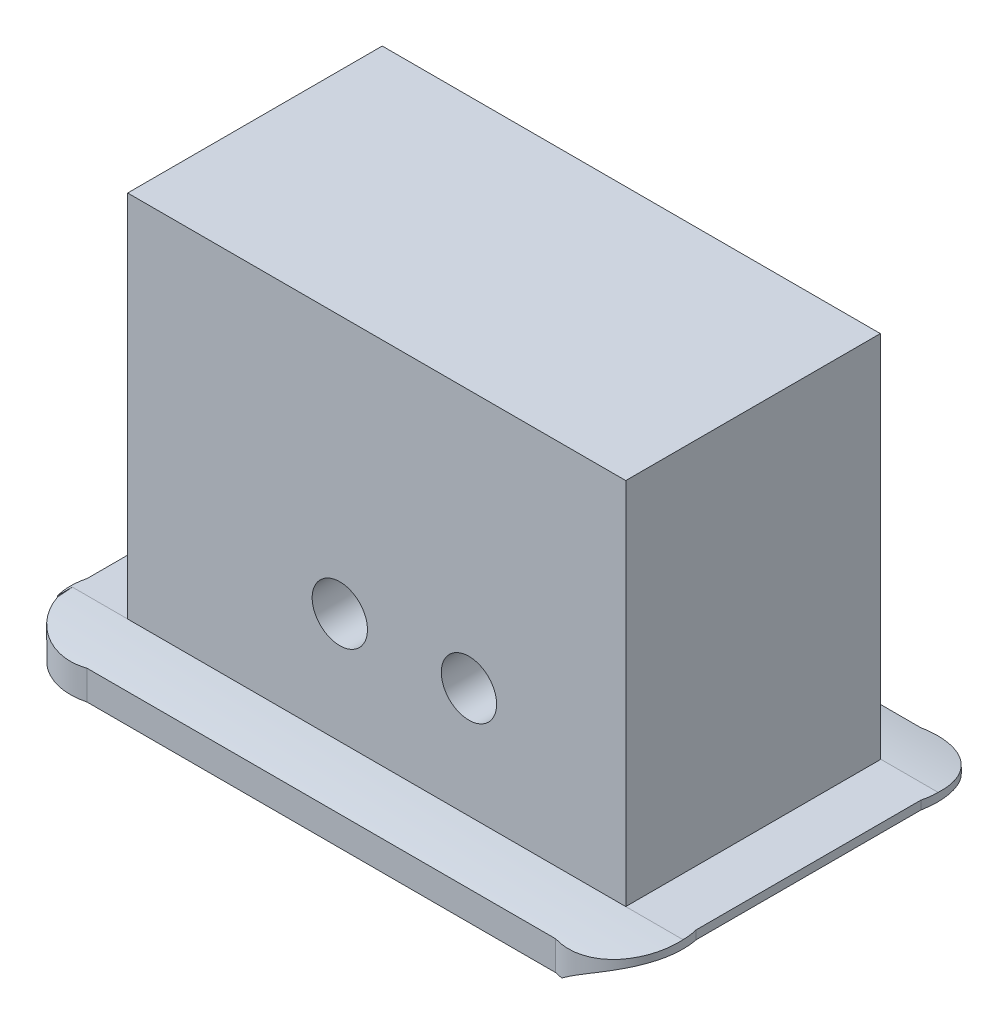
SolidWorks part; units mm, degrees
ref_plane "Front Plane" through (0, 0, 0) normal (0, 0, 1) x (1, 0, 0)
ref_plane "Top Plane" through (0, 0, 0) normal (0, 1, 0) x (1, 0, 0)
ref_plane "Right Plane" through (0, 0, 0) normal (1, 0, 0) x (0, 0, -1)
sketch "Sketch1" plane through (0, 0, 0) normal (0, 1, 0) x (1, 0, 0)
  line L0 (-3, 10.8) -> (24, 10.8)
  line L1 (0, 7.8) -> (21, 7.8)
  line L2 (0, 7.8) -> (0, 0)
  line L3 (0, 0) -> (21, 0)
  line L4 (21, 7.8) -> (21, 0)
  line L9 (24, 10.8) -> (24, -3)
  line L10 (-3, -3) -> (24, -3)
  line L11 (-3, 10.8) -> (-3, -3)
  dimension "D1" = 21
  dimension "D2" = 7.8
  dimension "D3" = 3
extrude "Boss-Extrude1" add sketch "Sketch1" along normal blind 22
sketch "Sketch3" plane through (0, 22, 0) normal (0, 1, 0) x (1, 0, 0)
  line L0 (0, 0) -> (21, 0) construction
  line L1 (21, 0) -> (21, 7.8) construction
  line L2 (21, 7.8) -> (0, 7.8) construction
  line L3 (0, 7.8) -> (0, 0) construction
  line L4 (0, 0) -> (21, 0)
  line L5 (21, 0) -> (21, 7.8)
  line L6 (21, 7.8) -> (0, 7.8)
  line L7 (0, 7.8) -> (0, 0)
extrude "Boss-Extrude2" add sketch "Sketch3" against normal blind 2
sketch "Sketch4" plane through (0, 22, 0) normal (0, 1, 0) x (1, 0, 0)
  line L1 (4.1034, 3.9) -> (4.1034, 10.8) construction
  line L2 (24, 10.8) -> (-3, 10.8) construction
  line L3 (4.1034, 3.9) -> (4.1034, -3) construction
  line L4 (-3, -3) -> (24, -3) construction
  circle A0 centre (4.1034, 3.9) radius 3
  dimension "D1" = 6
sketch "Sketch6" plane through (0, 0, 0) normal (0, -1, 0) x (1, 0, 0)
  line L4 (-3, -3.9) -> (31.2377, -3.9) construction
  line L5 (-3, -10.8) -> (-3, 3) construction
  line L6 (10.5, 3) -> (10.5, -26.2462) construction
  line L7 (-3, 3) -> (24, 3) construction
  line L8 (-6, 6) -> (-6, -13.8)
  line L9 (-6, -13.8) -> (27, -13.8)
  line L10 (27, -13.8) -> (27, 6)
  line L11 (27, 6) -> (-6, 6)
  line L12 (-6, 2.2) -> (-6, -10)
  line L13 (-2.2, -13.8) -> (23.2, -13.8)
  line L14 (27, -10) -> (27, 2.2)
  line L15 (23.2, 6) -> (-2.2, 6)
  line L16 (24, -10.8) -> (-3, -10.8) construction
  line L17 (24, 3) -> (24, -10.8) construction
  line L18 (-3, -10.8) -> (-3, 3)
  line L19 (24, -10.8) -> (-3, -10.8)
  line L20 (24, 3) -> (24, -10.8)
  line L21 (-3, 3) -> (24, 3)
  arc A0 (27, 2.2) -> (23.2, 6) centre (24, 3) ccw
  arc A1 (27, -10) -> (23.2, -13.8) centre (24, -10.8) cw
  arc A2 (-6, -10) -> (-2.2, -13.8) centre (-3, -10.8) ccw
  arc A3 (-6, 2.2) -> (-2.2, 6) centre (-3, 3) cw
  dimension "D1" = 3
extrude "Boss-Extrude3" add sketch "Sketch6" against normal blind 2
sketch "Sketch7" plane through (0, 0, -10.8) normal (0, 0, -1) x (-1, 0, 0)
  line L0 (2.2, 0) -> (-23.2, 0) construction
  line L2 (-21, 20) -> (-21, 0) construction
  circle A0 centre (-15.5, 8) radius 1.5
  circle A1 centre (-8.5, 8) radius 1.5
  point P8 (-22.6424, 2.786)
  dimension "D3" = 3
  dimension "D4" = 3
  dimension "D1" = 8
  dimension "D2" = 8
  dimension "D5" = 7
  dimension "D6" = 5.5
sketch "Sketch8" plane through (-3, 0, 0) normal (-1, 0, 0) x (0, 0, 1)
  line L0 (-3.9, 16.8165) -> (3, 16.8165) construction
  line L1 (3, 22) -> (3, 2) construction
  line L2 (-3.9, 16.8165) -> (-10.8, 16.8165) construction
  line L3 (-10.8, 22) -> (-10.8, 2) construction
  circle A0 centre (-3.9, 16.8165) radius 3
  point P2 (-3.9, 16.2692)
  point P11 (-3.9, 16.8165)
  dimension "D1" = 6
extrude "Cut-Extrude2" cut sketch "Sketch8" against normal blind 5
ref_plane "Plane3" through (27, 0, -10) normal (0, 0, 1) x (1, 0, 0)
sketch "Sketch12" plane through (-6, 0, 0) normal (-1, 0, 0) x (0, 0, 1)
  line L0 (3, 2) -> (6.1048, 2)
  line L1 (6.1048, 2) -> (6.1048, 1.5668)
  line L2 (6.1048, 0) -> (6.1048, 2) construction
  line L3 (-3.9145, 16.7797) -> (-3.9145, -4.906) construction
  line L4 (-13.9338, 2) -> (-13.9338, 1.5668)
  line L5 (-10.8289, 2) -> (-13.9338, 2)
  circle A0 centre (-3.9145, -58.1923) radius 60 construction
  spline S0 degree 2 poles (6.1048, 1.5668) (4.5709, 1.8985) (3, 2) knots 0 0 0 1 1 1
  spline S1 degree 2 poles (-13.9338, 1.5668) (-12.3999, 1.8985) (-10.8289, 2) knots 0 0 0 1 1 1
  point P12 (-13.9338, 1.5668)
  point P13 (-13.2234, 1.6761)
  point P14 (5.4292, 1.7014)
  dimension "D1" = 120
extrude "Cut-Extrude3" cut sketch "Sketch12" against normal blind 45
sketch "Sketch13" plane through (27, 0, -10) normal (0, 0, 1) x (1, 0, 0)
  line L2 (-3.3779, 0) -> (0.5096, 0)
  line L3 (0.5096, 0) -> (0.5096, 1.5757)
  line L4 (0.5096, 1.5757) -> (0.1756, 1.5757)
  spline S0 degree 3 poles (-3.3779, 0) (-2.3375, 0.8071) (-1.0904, 1.274) (0.1756, 1.5757) knots 0 0 0 0 1 1 1 1
  point P2 (-1.2143, 0.5398)
  point P7 (-1.4597, 0.7027)
  point P8 (-0.1173, 1.1945)
  point P10 (-0.4608, 1.2169)
  point P11 (-1.7044, 0.8429)
  point P12 (-0.6256, 1.3598)
  point P13 (-1.9562, 0.857)
extrude "Cut-Extrude5" cut sketch "Sketch13" against normal blind 45 and the other way blind 45
extrude "Cut-Extrude6" cut sketch "Sketch7" against normal through all both and the other way through all contours A1 | A0 region at (8.5, 8, -10.8)
